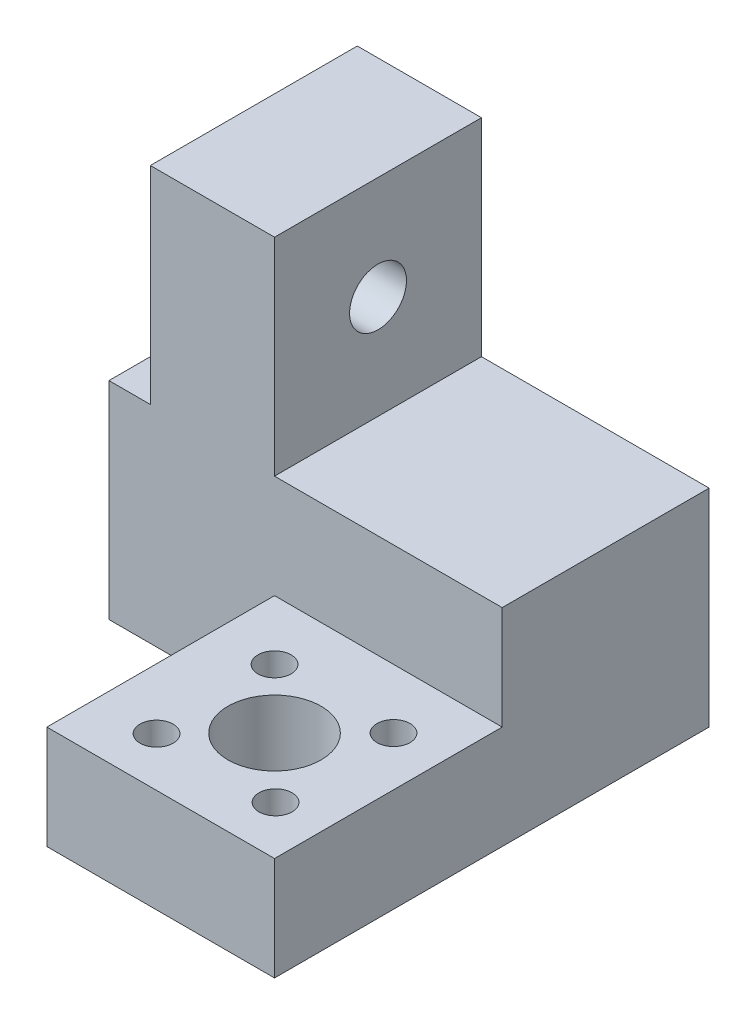
SolidWorks part; units mm, degrees
ref_plane "Front Plane" through (0, 0, 0) normal (0, 0, 1) x (1, 0, 0)
ref_plane "Top Plane" through (0, 0, 0) normal (0, 1, 0) x (1, 0, 0)
ref_plane "Right Plane" through (0, 0, 0) normal (1, 0, 0) x (0, 0, -1)
sketch "Sketch1" plane through (0, 0, 0) normal (0, 1, 0) x (1, 0, 0)
  line L1 (-11, 11) -> (11, 11)
  line L2 (-11, 11) -> (-11, -11)
  line L3 (-11, -11) -> (11, -11)
  line L4 (11, 11) -> (11, -11)
  circle A0 centre (0, 0) radius 11 construction
  circle A1 centre (-5.25, 5.25) radius 1.6
  circle A2 centre (6.25, 5.25) radius 1.6
  circle A3 centre (6.3486, -6.25) radius 1.6
  circle A5 centre (-5.1514, -6.25) radius 1.6
  dimension "D1" = 22
  dimension "D2" = 3.2
  dimension "D3" = 11.5
  dimension "D4" = 11.5
  dimension "D5" = 11.5
  dimension "D6" = 11.5
  dimension "D7" = 5.25
  dimension "D8" = 5.25
extrude "Boss-Extrude1" add sketch "Sketch1" along normal blind 10
sketch "Sketch2" plane through (0, 0, -11) normal (0, 0, -1) x (-1, 0, 0)
  line L1 (-11, 0) -> (27, 0)
  line L2 (-11, 0) -> (-11, 20)
  line L3 (-11, 20) -> (27, 20)
  line L4 (27, 0) -> (27, 20)
  dimension "D1" = 20
  dimension "D2" = 38
extrude "Boss-Extrude2" add sketch "Sketch2" along normal blind 20
sketch "Sketch3" plane through (0, 20, 0) normal (0, 1, 0) x (1, 0, 0)
  line L0 (-27, 11) -> (11, 11) construction
  line L1 (-23, 11) -> (-11, 11)
  line L2 (-23, 11) -> (-23, 31)
  line L3 (-23, 31) -> (-11, 31)
  line L4 (-11, 11) -> (-11, 31)
  line L5 (11, 31) -> (11, 11) construction
  dimension "D1" = 20
  dimension "D2" = 12
  dimension "D3" = 22
extrude "Boss-Extrude3" add sketch "Sketch3" along normal blind 20
sketch "Sketch4" plane through (-11, 0, 0) normal (1, 0, 0) x (0, 0, -1)
  line L0 (11, 20) -> (31, 20) construction
  line L1 (31, 40) -> (31, 20) construction
  circle A0 centre (21, 30) radius 2.75
  point P6 (31, 30)
  dimension "D1" = 5.5
  dimension "D3" = 10
  dimension "D2" = 10
extrude "Cut-Extrude1" cut sketch "Sketch4" against normal through all
sketch "Sketch5" plane through (0, 10, 0) normal (0, 1, 0) x (1, 0, 0)
  circle A0 centre (0.5, -0.5) radius 4.5
  circle A2 centre (-5.25, 5.25) radius 1.6 construction
  dimension "D1" = 9
  dimension "D2" = 5.75
  dimension "D3" = 5.75
extrude "Cut-Extrude2" cut sketch "Sketch5" against normal through all
